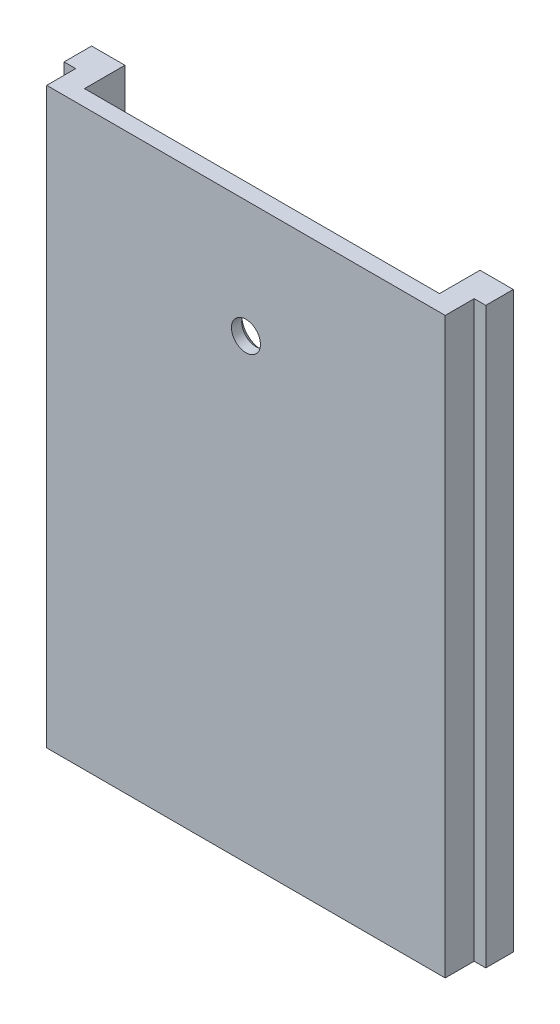
SolidWorks part; units mm, degrees
ref_plane "Alzado" through (0, 0, 0) normal (0, 0, 1) x (1, 0, 0)
ref_plane "Planta" through (0, 0, 0) normal (0, 1, 0) x (1, 0, 0)
ref_plane "Vista lateral" through (0, 0, 0) normal (1, 0, 0) x (0, 0, -1)
sketch "Croquis1" plane through (0, 0, 0) normal (0, 1, 0) x (1, 0, 0)
  line L5 (-4, 10) -> (-4, 19.5)
  line L14 (7.5, 19.5) -> (7.5, 5.5361)
  line L17 (-4, 19.5) -> (7.5, 19.5)
  line L19 (0, 0) -> (137.5, 0)
  line L20 (0, 0) -> (0, 10)
  line L21 (0, 10) -> (-4, 10)
  line L23 (7.5, 5.5361) -> (130, 5.5361)
  line L25 (68.75, 54.2093) -> (68.75, -41.2998) construction
  line L26 (137.5, 10) -> (141.5, 10)
  line L27 (137.5, 0) -> (137.5, 10)
  line L28 (141.5, 19.5) -> (130, 19.5)
  line L29 (130, 19.5) -> (130, 5.5361)
  line L30 (141.5, 10) -> (141.5, 19.5)
  point P3 (68.75, 5.5361)
  point P12 (68.75, 0)
  dimension "D1" = 68.75
  dimension "D2" = 10
  dimension "D3" = 9.5
  dimension "D4" = 11.5
  dimension "D5" = 72.75
  dimension "D7" = 5.5361
extrude "Saliente-Extruir4" add sketch "Croquis1" along normal blind 198 contours L17 L14 L23 L29 L28 L30 L26 L27 L19 L20 L21 L5
ref_plane "Plano1" through (68.75, 0, 0) normal (1, 0, 0) x (0, 0, -1)
sketch "Croquis2" plane through (0, 0, -5.5361) normal (0, 0, -1) x (-1, 0, 0)
  line L0 (-7.5, 0) -> (-130, 0) construction
  line L1 (-7.5, 0) -> (-130, 0) construction
  line L2 (-7.5, 198) -> (-7.5, 0) construction
  line L3 (-130, 198) -> (-130, 0) construction
  line L4 (-7.5, 198) -> (-7.5, 0) construction
  line L5 (-130, 198) -> (-130, 0) construction
  line L6 (-130, 108) -> (-7.5, 108)
  line L7 (-130, 105) -> (-7.5, 105)
  line L8 (-130, 108) -> (-130, 105)
  line L9 (-7.5, 108) -> (-7.5, 105)
  dimension "D1" = 108
  dimension "D2" = 3
extrude "Saliente-Extruir5" add sketch "Croquis2" along normal up to surface (13.9639 mm away) up to face at (135.75, 99, -19.5)
sketch "Croquis3" plane through (0, 0, 0) normal (0, 0, 1) x (1, 0, 0)
  line L0 (68.75, 198) -> (68.75, 0) construction
  line L1 (0, 198) -> (137.5, 198) construction
  line L2 (0, 0) -> (137.5, 0) construction
  circle A0 centre (68.75, 157.453) radius 5
  dimension "D1" = 10
extrude "Cortar-Extruir1" cut sketch "Croquis3" against normal blind 10
chamfer "Chaflán2" distance 2 angle 45 1 edges at (63.75, 157.453, -5.5361)
sketch "Croquis4" plane through (0, 0, 0) normal (0, 0, 1) x (1, 0, 0)
  line L0 (68.75, 157.453) -> (68.75, 0) construction
  line L5 (0, 0) -> (137.5, 0) construction
  line L7 (118.75, 43.7265) -> (18.75, 43.7265)
  line L8 (118.75, 43.7265) -> (118.75, 113.7265)
  line L9 (118.75, 113.7265) -> (18.75, 113.7265)
  line L10 (18.75, 43.7265) -> (18.75, 113.7265)
  line L11 (118.75, 43.7265) -> (18.75, 113.7265) construction
  line L12 (118.75, 113.7265) -> (18.75, 43.7265) construction
  point P4 (68.75, 78.7265)
  dimension "D1" = 100
  dimension "D2" = 70
